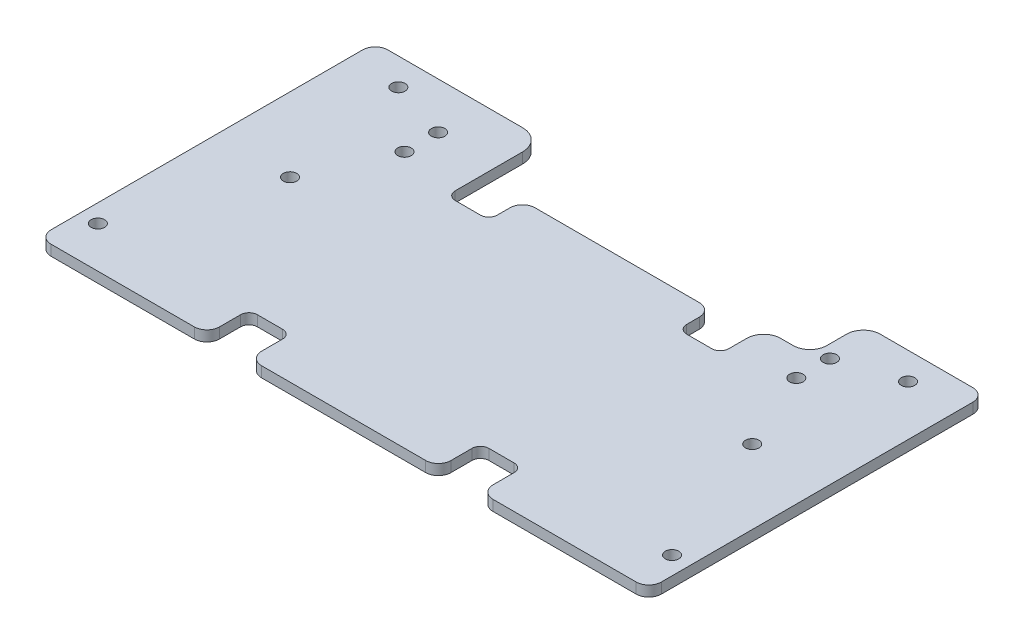
SolidWorks part; units mm, degrees
ref_plane "Front Plane" through (0, 0, 0) normal (0, 0, 1) x (1, 0, 0)
ref_plane "Top Plane" through (0, 0, 0) normal (0, 1, 0) x (1, 0, 0)
ref_plane "Right Plane" through (0, 0, 0) normal (1, 0, 0) x (0, 0, -1)
sketch "Sketch1" plane through (0, 0, 0) normal (0, 1, 0) x (1, 0, 0)
  line L0 (0, 0) -> (0, -101.6)
  line L1 (0, -101.6) -> (184.15, -101.6)
  line L2 (184.15, -101.6) -> (184.15, 0)
  line L4 (50.8, 0) -> (50.8, -19.05)
  line L5 (50.8, -19.05) -> (133.35, -19.05)
  line L6 (133.35, -19.05) -> (133.35, 0)
  line L7 (0, 0) -> (50.8, 0)
  line L8 (133.35, 0) -> (184.15, 0)
  line L9 (50.8, -19.05) -> (50.8, -29.21)
  line L10 (50.8, -29.21) -> (63.5, -29.21)
  line L11 (63.5, -29.21) -> (63.5, -19.05)
  line L12 (133.35, -19.05) -> (133.35, -29.21)
  line L13 (133.35, -29.21) -> (120.65, -29.21)
  line L14 (120.65, -29.21) -> (120.65, -19.05)
  line L15 (50.8, -101.6) -> (50.8, -88.9)
  line L16 (50.8, -88.9) -> (63.5, -88.9)
  line L17 (63.5, -88.9) -> (63.5, -101.6)
  line L18 (120.65, -101.6) -> (120.65, -88.9)
  line L19 (120.65, -88.9) -> (133.35, -88.9)
  line L20 (133.35, -88.9) -> (133.35, -101.6)
  line L21 (92.075, -101.6) -> (92.075, -19.05) construction
  dimension "D1" = 184.15
  dimension "D2" = 82.55
  dimension "D3" = 12.7
  dimension "D4" = 10.16
  dimension "D5" = 19.05
  dimension "D6" = 101.6
  dimension "D7" = 12.7
extrude "Boss-Extrude1" add sketch "Sketch1" along normal blind 3.175 contours L2 L0 L1 | L21 L1 L18 L19 L20 L2 L8 L6 L12 L13 L14 L5 region at (43.2352, 0, 54.2701) region at (140.9148, 0, 54.2701)
fillet "Fillet1" radius 3.81 4 edges at (184.15, 1.5875, 101.6) (0, 1.5875, 101.6) (184.15, 1.5875, 0) (0, 1.5875, 0)
sketch "Sketch2" plane through (0, 3.175, 0) normal (0, 1, 0) x (1, 0, 0)
  line L0 (92.075, -101.6) -> (92.075, -19.05) construction
  line L1 (63.5, -101.6) -> (120.65, -101.6) construction
  line L2 (63.5, -19.05) -> (120.65, -19.05) construction
  circle A4 centre (5.4374, -89.1463) radius 2.032 construction
  circle A5 centre (5.4374, -89.1463) radius 2.032
  circle A6 centre (22.3389, -48.035) radius 2.032 construction
  circle A7 centre (178.7126, -89.1463) radius 2.032
  circle A8 centre (15.1663, -8.1952) radius 2.032 construction
  circle A9 centre (22.3389, -48.035) radius 2.032
  circle A11 centre (15.1663, -8.1952) radius 2.032
  circle A24 centre (32.9463, -24.13) radius 2.032 construction
  circle A25 centre (32.9463, -13.97) radius 2.032 construction
  circle A26 centre (32.9463, -24.13) radius 2.032
  circle A27 centre (32.9463, -13.97) radius 2.032
  circle A34 centre (32.9463, -13.97) radius 2.032
  circle A35 centre (32.9463, -24.13) radius 2.032
  circle A37 centre (161.8111, -48.035) radius 2.032
  circle A38 centre (151.2037, -24.13) radius 2.032
  circle A39 centre (151.2037, -13.97) radius 2.032
  circle A40 centre (168.9837, -8.1952) radius 2.032
extrude "Cut-Extrude1" cut sketch "Sketch2" against normal through all contours A11 | A9 | A5 | A26 | A27 | A37 | A38 | A7 | A39 | A40 region at (5.4374, 3.175, 89.1463) region at (22.3389, 3.175, 48.035) region at (15.1663, 3.175, 8.1952) region at (32.9463, 3.175, 24.13) region at (32.9463, 3.175, 13.97)
fillet "Fillet2" radius 6.35 2 edges at (50.8, 1.5875, 0) (133.35, 1.5875, 0)
fillet "Fillet3" radius 2.54 8 edges at (133.35, 1.5875, 29.21) (120.65, 1.5875, 29.21) (50.8, 1.5875, 29.21) (63.5, 1.5875, 29.21) (133.35, 1.5875, 88.9) (120.65, 1.5875, 88.9) (63.5, 1.5875, 88.9) (50.8, 1.5875, 88.9)
fillet "Fillet4" radius 3.81 2 edges at (120.65, 1.5875, 19.05) (63.5, 1.5875, 19.05)
fillet "Fillet5" radius 3.81 4 edges at (133.35, 1.5875, 101.6) (120.65, 1.5875, 101.6) (63.5, 1.5875, 101.6) (50.8, 1.5875, 101.6)
ref_plane "Plane1" through (0, 2.8036, -1.0204) normal (0, 0.9397, -0.342) x (1, 0, 0)
sketch "Sketch8" plane through (0, 0, 0) normal (0, -1, 0) x (1, 0, 0)
  line L0 (139.7, 14.8488) -> (146.05, 14.8488) construction
  line L1 (139.7, 14.8488) -> (146.05, 14.8488)
  line L2 (139.7, 14.8488) -> (139.7, 0)
  line L3 (146.05, 14.8488) -> (146.05, 0)
  line L4 (139.7, 0) -> (180.34, 0) construction
  line L5 (147.32, 16.1188) -> (147.32, 0)
  line L6 (138.43, 16.1188) -> (147.32, 16.1188)
  line L7 (138.43, 16.1188) -> (138.43, 0)
  line L8 (138.43, 16.1188) -> (133.35, 16.1188)
  line L9 (133.35, 26.67) -> (133.35, 6.35) construction
  line M40 (133.35, 26.67) -> (133.35, 6.35)
  arc M41 (133.35, 6.35) -> (139.7, 0) centre (139.7, 6.35) ccw
  line M42 (139.7, 0) -> (180.34, 0)
  dimension "D1" = 1.27
extrude "Cut-Extrude4" cut sketch "Sketch8" against normal through all contours L6 L7 L2 L1 L3 L5 M41 M42 | L3 L1 L2 M42 | L7 L8 M40 M41 region at (139.5159, 0, 7.4244) region at (142.875, 0, 7.4244) region at (136.0245, 0, 8.8376)
fillet "Fillet9" radius 5.08 3 edges at (133.35, 1.5875, 16.1188) (147.32, 1.5875, 0) (147.32, 1.5875, 16.1188)
